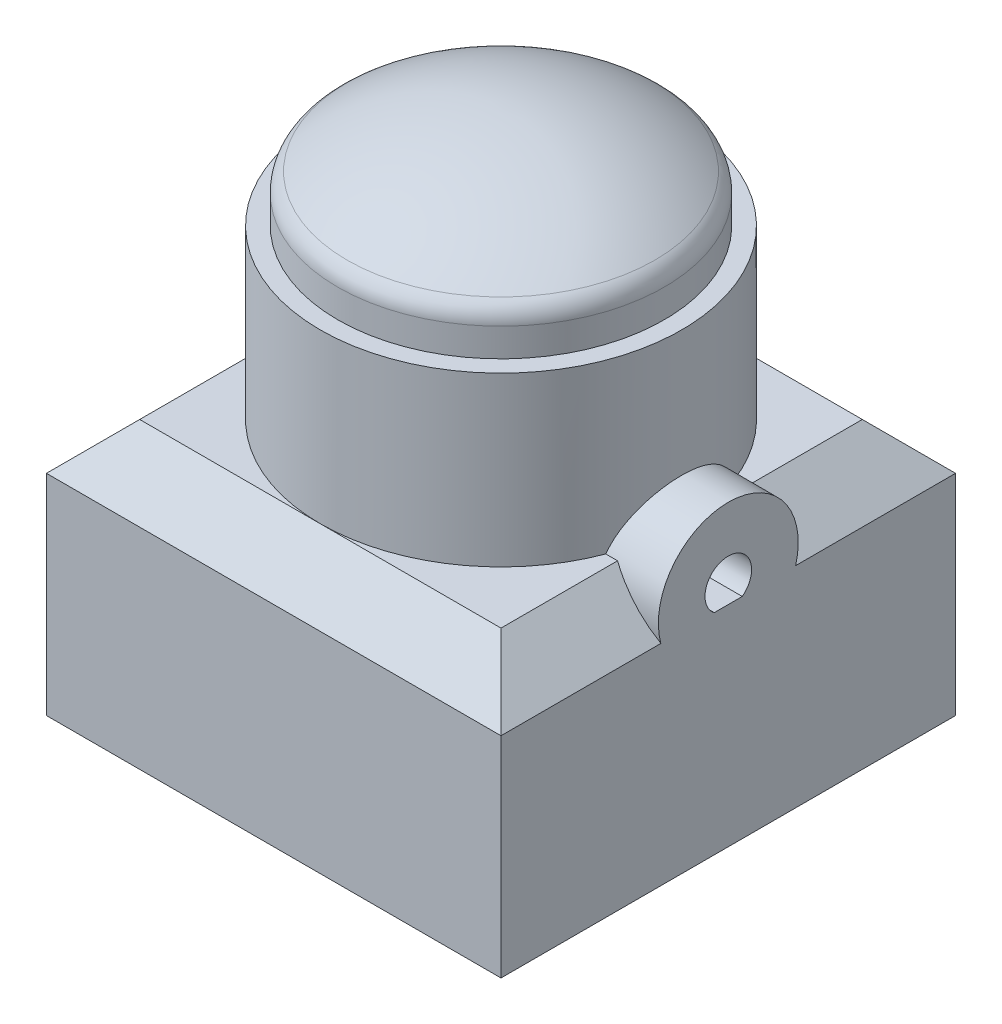
SolidWorks part; units mm, degrees
ref_plane "Alzado" through (0, 0, 0) normal (0, 0, 1) x (1, 0, 0)
ref_plane "Planta" through (0, 0, 0) normal (0, 1, 0) x (1, 0, 0)
ref_plane "Vista lateral" through (0, 0, 0) normal (1, 0, 0) x (0, 0, -1)
sketch "Croquis1" plane through (0, 0, 0) normal (0, 1, 0) x (1, 0, 0)
  line L1 (-9.75, -9.75) -> (9.75, -9.75)
  line L2 (-9.75, -9.75) -> (-9.75, 9.75)
  line L3 (-9.75, 9.75) -> (9.75, 9.75)
  line L4 (9.75, -9.75) -> (9.75, 9.75)
  line L5 (-9.75, -9.75) -> (9.75, 9.75) construction
  line L6 (-9.75, 9.75) -> (9.75, -9.75) construction
  point P0 (0, 0)
  dimension "D1" = 19.5
  dimension "D2" = 19.5
extrude "Saliente-Extruir1" add sketch "Croquis1" along normal blind 11
chamfer "Chaflán1" distance 2 angle 45 4 edges at (-9.75, 11, 0) (0, 11, -9.75) (9.75, 11, 0) (0, 11, 9.75)
sketch "Croquis2" plane through (9.75, 0, 0) normal (1, 0, 0) x (0, 0, -1)
  line L0 (0, 9) -> (0, 9.8)
  line L1 (9.75, 9) -> (-9.75, 9) construction
  circle A0 centre (0, 9.8) radius 1
  circle A1 centre (0, 9.8) radius 3
  line M3 (9.75, 9) -> (-9.75, 9)
  dimension "D2" = 2
  dimension "D3" = 6
  dimension "D1" = 0.8
extrude "Saliente-Extruir2" add sketch "Croquis2" against normal blind 9 contours A1 A0 M3 region at (9.75, 10.8043, 0)
sketch "Croquis3" plane through (0, 11, 0) normal (0, 1, 0) x (1, 0, 0)
  circle A0 centre (0, 0) radius 7.75
  dimension "D1" = 15.5
extrude "Saliente-Extruir3" add sketch "Croquis3" along normal blind 7.2
sketch "Croquis4" plane through (9.75, 0, 0) normal (1, 0, 0) x (0, 0, -1)
  line L0 (-0.6, 9) -> (0.6, 9)
  arc A0 (0.6, 9) -> (-0.6, 9) centre (0, 9.8) ccw
extrude "Cortar-Extruir1" cut sketch "Croquis4" against normal blind 3.2
sketch "Croquis5" plane through (0, 18.2, 0) normal (0, 1, 0) x (1, 0, 0)
  circle A0 centre (0, 0) radius 7
  dimension "D1" = 14
extrude "Saliente-Extruir4" add sketch "Croquis5" along normal blind 1.7
dome "Cúpula1" faces to dome 1 distance 2.5 reverse direction no elliptical dome no face at (0, 19.9, 7) parameters "D1"=2.5
fillet "Redondeo1" radius 1 1 edges at (0, 19.9, 7)
